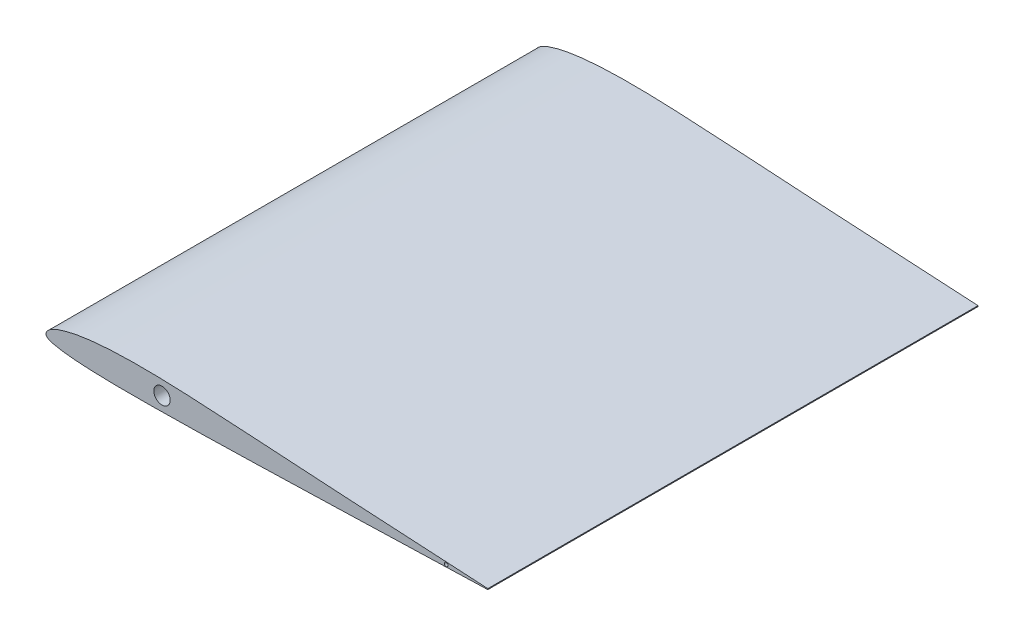
SolidWorks part; units mm, degrees
material "Polyurethane Foam Flexible"
ref_plane "Front Plane" through (0, 0, 0) normal (0, 0, 1) x (1, 0, 0)
ref_plane "Top Plane" through (0, 0, 0) normal (0, 1, 0) x (1, 0, 0)
ref_plane "Right Plane" through (0, 0, 0) normal (1, 0, 0) x (0, 0, -1)
curve "ht32-8-imported"
  spline degree 3 poles (203.2026, 0.2115, 0) (202.75, 0.2358, 0) (201.4822, 0.3036, 0) (199.2299, 0.4276, 0) (196.3046, 0.5865, 0) (192.9787, 0.7694, 0) (189.375, 0.9706, 0) (185.6129, 1.1785, 0) (181.7737, 1.3957, 0) (177.8996, 1.6147, 0) (174.01, 1.8354, 0) (170.1132, 2.0552, 0) (166.2133, 2.2775, 0) (162.3117, 2.4986, 0) (158.4107, 2.722, 0) (154.5106, 2.9441, 0) (150.6142, 3.1678, 0) (146.7204, 3.3936, 0) (142.8309, 3.617, 0) (138.944, 3.8454, 0) (135.0595, 4.0721, 0) (131.1775, 4.3012, 0) (127.2967, 4.5315, 0) (123.4189, 4.7649, 0) (119.5421, 5.0008, 0) (115.6675, 5.2398, 0) (111.7949, 5.4816, 0) (107.9236, 5.7247, 0) (104.0572, 5.9681, 0) (100.1894, 6.212, 0) (96.3188, 6.4543, 0) (92.4477, 6.6946, 0) (88.584, 6.9322, 0) (84.7415, 7.1637, 0) (80.9229, 7.3889, 0) (77.3978, 7.5906, 0) (74.5229, 7.7493, 0) (71.9946, 7.8843, 0) (69.1241, 8.0324, 0) (65.5083, 8.2076, 0) (61.4852, 8.3831, 0) (57.5218, 8.5328, 0) (53.6734, 8.652, 0) (49.9058, 8.739, 0) (46.181, 8.7912, 0) (42.491, 8.8047, 0) (38.8468, 8.7742, 0) (35.2596, 8.6962, 0) (31.7561, 8.5671, 0) (28.3661, 8.3856, 0) (25.1292, 8.152, 0) (22.0798, 7.8688, 0) (19.2587, 7.5428, 0) (16.7019, 7.1837, 0) (14.4336, 6.8058, 0) (12.4541, 6.4216, 0) (10.7471, 6.0418, 0) (9.283, 5.6741, 0) (8.0264, 5.3216, 0) (6.9394, 4.9844, 0) (5.9876, 4.6599, 0) (5.1429, 4.3427, 0) (4.3754, 4.0301, 0) (3.6577, 3.7081, 0) (2.9646, 3.3607, 0) (2.2868, 2.9708, 0) (1.6384, 2.5305, 0) (1.05, 2.0355, 0) (0.5511, 1.4823, 0) (0.1821, 0.8795, 0) (0.0202, 0.3651, 0) (-0.0065, -0.0193, 0) (0.0194, -0.3136, 0) (0.1268, -0.6144, 0) (0.297, -0.8546, 0) (0.4742, -1.036, 0) (0.6922, -1.2054, 0) (0.9846, -1.3848, 0) (1.3525, -1.5668, 0) (1.7794, -1.7448, 0) (2.2605, -1.9172, 0) (2.8067, -2.0876, 0) (3.4413, -2.2602, 0) (4.1881, -2.438, 0) (5.0669, -2.6215, 0) (6.0922, -2.8069, 0) (7.2766, -2.9931, 0) (8.6343, -3.178, 0) (10.1869, -3.3594, 0) (11.9608, -3.5369, 0) (13.9882, -3.7077, 0) (16.2949, -3.8689, 0) (18.8937, -4.0155, 0) (21.7662, -4.1437, 0) (24.8729, -4.2492, 0) (28.1584, -4.3297, 0) (31.5775, -4.3867, 0) (35.0914, -4.4207, 0) (38.6791, -4.4351, 0) (42.3216, -4.4311, 0) (46.0126, -4.4125, 0) (49.7579, -4.3795, 0) (53.5805, -4.3372, 0) (57.5149, -4.2842, 0) (61.5959, -4.2202, 0) (65.8841, -4.1445, 0) (69.584, -4.0721, 0) (72.8088, -4.005, 0) (75.5799, -3.9448, 0) (78.7708, -3.8727, 0) (82.2137, -3.7909, 0) (85.8123, -3.7021, 0) (89.4548, -3.6091, 0) (93.1502, -3.5116, 0) (96.8889, -3.4111, 0) (100.657, -3.3069, 0) (104.4397, -3.2018, 0) (108.2248, -3.0945, 0) (112.0082, -2.9863, 0) (115.791, -2.8766, 0) (119.5782, -2.7658, 0) (123.3765, -2.6523, 0) (127.1945, -2.5376, 0) (131.0416, -2.42, 0) (134.9198, -2.302, 0) (138.8194, -2.1823, 0) (142.7263, -2.0602, 0) (146.6334, -1.9373, 0) (150.5405, -1.8169, 0) (154.4476, -1.6935, 0) (158.3547, -1.5735, 0) (162.2615, -1.4515, 0) (166.1675, -1.3317, 0) (170.0718, -1.2089, 0) (173.9729, -1.0897, 0) (177.8669, -0.9678, 0) (181.7453, -0.8488, 0) (185.5889, -0.7312, 0) (189.3549, -0.6169, 0) (192.9626, -0.5096, 0) (196.292, -0.413, 0) (199.2203, -0.3248, 0) (201.4752, -0.2617, 0) (202.7443, -0.2247, 0) (203.1974, -0.2115, 0) knots 0 0 0 0 0.003316 0.009286 0.0165 0.024744 0.033651 0.0429 0.052304 0.061778 0.071282 0.080801 0.090326 0.099855 0.109385 0.118907 0.128429 0.137932 0.147436 0.156926 0.166412 0.175898 0.185369 0.194848 0.204314 0.213779 0.223243 0.232695 0.242152 0.25158 0.261042 0.270519 0.279949 0.289356 0.298677 0.307928 0.315183 0.319737 0.326448 0.336207 0.346216 0.355902 0.365219 0.374379 0.383467 0.392467 0.401369 0.410123 0.41871 0.427012 0.434953 0.442447 0.449411 0.455723 0.46133 0.466229 0.470471 0.47412 0.47727 0.480016 0.482444 0.484624 0.486615 0.488504 0.490376 0.492284 0.49422 0.496102 0.497896 0.499646 0.501237 0.501776 0.502457 0.503386 0.504071 0.504595 0.505236 0.506086 0.5071 0.508235 0.509467 0.510837 0.512419 0.514277 0.516452 0.518985 0.521897 0.525221 0.529007 0.53333 0.538261 0.543889 0.550243 0.557299 0.56492 0.57298 0.581338 0.589931 0.598683 0.607581 0.616575 0.625681 0.634977 0.644537 0.654462 0.664831 0.675908 0.681531 0.688425 0.696181 0.704877 0.713615 0.722511 0.731528 0.740655 0.749867 0.759101 0.768335 0.777565 0.786786 0.796016 0.805278 0.814581 0.823955 0.833431 0.842961 0.852492 0.862023 0.871554 0.881085 0.890615 0.900146 0.909675 0.9192 0.928718 0.938223 0.947696 0.9571 0.96635 0.975256 0.9835 0.990713 0.996685 1 1 1 1
sketch "Sketch3" plane through (0, 0, 0) normal (0, 0, 1) x (1, 0, 0)
  line L3 (203.2026, 0.2115) -> (203.1974, -0.2115)
  spline S0 degree 3 poles (356.7908, -2985.9067) (413.0686, 1.836) (306.2858, -5.4633) (199.2299, 0.4276) (196.3046, 0.5865) (192.9787, 0.7694) (189.375, 0.9706) (185.6129, 1.1785) (181.7737, 1.3957) (177.8996, 1.6147) (174.01, 1.8354) (170.1132, 2.0552) (166.2133, 2.2775) (162.3117, 2.4986) (158.4107, 2.722) (154.5106, 2.9441) (150.6142, 3.1678) (146.7204, 3.3936) (142.8309, 3.617) (138.944, 3.8454) (135.0595, 4.0721) (131.1775, 4.3012) (127.2967, 4.5315) (123.4189, 4.7649) (119.5421, 5.0008) (115.6675, 5.2398) (111.7949, 5.4816) (107.9236, 5.7247) (104.0572, 5.9681) (100.1894, 6.212) (96.3188, 6.4543) (92.4477, 6.6946) (88.584, 6.9322) (84.7415, 7.1637) (80.9229, 7.3889) (77.3978, 7.5906) (74.5229, 7.7493) (71.9946, 7.8843) (69.1241, 8.0324) (65.5083, 8.2076) (61.4852, 8.3831) (57.5218, 8.5328) (53.6734, 8.652) (49.9058, 8.739) (46.181, 8.7912) (42.491, 8.8047) (38.8468, 8.7742) (35.2596, 8.6962) (31.7561, 8.5671) (28.3661, 8.3856) (25.1292, 8.152) (22.0798, 7.8688) (19.2587, 7.5428) (16.7019, 7.1837) (14.4336, 6.8058) (12.4541, 6.4216) (10.7471, 6.0418) (9.283, 5.6741) (8.0264, 5.3216) (6.9394, 4.9844) (5.9876, 4.6599) (5.1429, 4.3427) (4.3754, 4.0301) (3.6577, 3.7081) (2.9646, 3.3607) (2.2868, 2.9708) (1.6384, 2.5305) (1.05, 2.0355) (0.5511, 1.4823) (0.1821, 0.8795) (0.0202, 0.3651) (-0.0065, -0.0193) (0.0194, -0.3136) (0.1268, -0.6144) (0.297, -0.8546) (0.4742, -1.036) (0.6922, -1.2054) (0.9846, -1.3848) (1.3525, -1.5668) (1.7794, -1.7448) (2.2605, -1.9172) (2.8067, -2.0876) (3.4413, -2.2602) (4.1881, -2.438) (5.0669, -2.6215) (6.0922, -2.8069) (7.2766, -2.9931) (8.6343, -3.178) (10.1869, -3.3594) (11.9608, -3.5369) (13.9882, -3.7077) (16.2949, -3.8689) (18.8937, -4.0155) (21.7662, -4.1437) (24.8729, -4.2492) (28.1584, -4.3297) (31.5775, -4.3867) (35.0914, -4.4207) (38.6791, -4.4351) (42.3216, -4.4311) (46.0126, -4.4125) (49.7579, -4.3795) (53.5805, -4.3372) (57.5149, -4.2842) (61.5959, -4.2202) (65.8841, -4.1445) (69.584, -4.0721) (72.8088, -4.005) (75.5799, -3.9448) (78.7708, -3.8727) (82.2137, -3.7909) (85.8123, -3.7021) (89.4548, -3.6091) (93.1502, -3.5116) (96.8889, -3.4111) (100.657, -3.3069) (104.4397, -3.2018) (108.2248, -3.0945) (112.0082, -2.9863) (115.791, -2.8766) (119.5782, -2.7658) (123.3765, -2.6523) (127.1945, -2.5376) (131.0416, -2.42) (134.9198, -2.302) (138.8194, -2.1823) (142.7263, -2.0602) (146.6334, -1.9373) (150.5405, -1.8169) (154.4476, -1.6935) (158.3547, -1.5735) (162.2615, -1.4515) (166.1675, -1.3317) (170.0718, -1.2089) (173.9729, -1.0897) (177.8669, -0.9678) (181.7453, -0.8488) (185.5889, -0.7312) (189.3549, -0.6169) (192.9626, -0.5096) (196.292, -0.413) (199.2203, -0.3248) (315.412, 2.9269) (430.2694, 18.2159) (630.7155, -2957.7378) knots -0.767748 -0.767748 -0.767748 -0.767748 0.003316 0.009286 0.0165 0.024744 0.033651 0.0429 0.052304 0.061778 0.071282 0.080801 0.090326 0.099855 0.109385 0.118907 0.128429 0.137932 0.147436 0.156926 0.166412 0.175898 0.185369 0.194848 0.204314 0.213779 0.223243 0.232695 0.242152 0.25158 0.261042 0.270519 0.279949 0.289356 0.298677 0.307928 0.315183 0.319737 0.326448 0.336207 0.346216 0.355902 0.365219 0.374379 0.383467 0.392467 0.401369 0.410123 0.41871 0.427012 0.434953 0.442447 0.449411 0.455723 0.46133 0.466229 0.470471 0.47412 0.47727 0.480016 0.482444 0.484624 0.486615 0.488504 0.490376 0.492284 0.49422 0.496102 0.497896 0.499646 0.501237 0.501776 0.502457 0.503386 0.504071 0.504595 0.505236 0.506086 0.5071 0.508235 0.509467 0.510837 0.512419 0.514277 0.516452 0.518985 0.521897 0.525221 0.529007 0.53333 0.538261 0.543889 0.550243 0.557299 0.56492 0.57298 0.581338 0.589931 0.598683 0.607581 0.616575 0.625681 0.634977 0.644537 0.654462 0.664831 0.675908 0.681531 0.688425 0.696181 0.704877 0.713615 0.722511 0.731528 0.740655 0.749867 0.759101 0.768335 0.777565 0.786786 0.796016 0.805278 0.814581 0.823955 0.833431 0.842961 0.852492 0.862023 0.871554 0.881085 0.890615 0.900146 0.909675 0.9192 0.928718 0.938223 0.947696 0.9571 0.96635 0.975256 0.9835 0.990713 0.996685 1.83372 1.83372 1.83372 1.83372 only from (203.2026, 0.2115) to (203.1974, -0.2115) construction
  spline S1 degree 3 poles (203.2026, 0.2115) (202.75, 0.2358) (201.4822, 0.3036) (199.2299, 0.4276) (196.3046, 0.5865) (192.9787, 0.7694) (189.375, 0.9706) (185.6129, 1.1785) (181.7737, 1.3957) (177.8996, 1.6147) (174.01, 1.8354) (170.1132, 2.0552) (166.2133, 2.2775) (162.3117, 2.4986) (158.4107, 2.722) (154.5106, 2.9441) (150.6142, 3.1678) (146.7204, 3.3936) (142.8309, 3.617) (138.944, 3.8454) (135.0595, 4.0721) (131.1775, 4.3012) (127.2967, 4.5315) (123.4189, 4.7649) (119.5421, 5.0008) (115.6675, 5.2398) (111.7949, 5.4816) (107.9236, 5.7247) (104.0572, 5.9681) (100.1894, 6.212) (96.3188, 6.4543) (92.4477, 6.6946) (88.584, 6.9322) (84.7415, 7.1637) (80.9229, 7.3889) (77.3978, 7.5906) (74.5229, 7.7493) (71.9946, 7.8843) (69.1241, 8.0324) (65.5083, 8.2076) (61.4852, 8.3831) (57.5218, 8.5328) (53.6734, 8.652) (49.9058, 8.739) (46.181, 8.7912) (42.491, 8.8047) (38.8468, 8.7742) (35.2596, 8.6962) (31.7561, 8.5671) (28.3661, 8.3856) (25.1292, 8.152) (22.0798, 7.8688) (19.2587, 7.5428) (16.7019, 7.1837) (14.4336, 6.8058) (12.4541, 6.4216) (10.7471, 6.0418) (9.283, 5.6741) (8.0264, 5.3216) (6.9394, 4.9844) (5.9876, 4.6599) (5.1429, 4.3427) (4.3754, 4.0301) (3.6577, 3.7081) (2.9646, 3.3607) (2.2868, 2.9708) (1.6384, 2.5305) (1.05, 2.0355) (0.5511, 1.4823) (0.1821, 0.8795) (0.0202, 0.3651) (-0.0065, -0.0193) (0.0194, -0.3136) (0.1268, -0.6144) (0.297, -0.8546) (0.4742, -1.036) (0.6922, -1.2054) (0.9846, -1.3848) (1.3525, -1.5668) (1.7794, -1.7448) (2.2605, -1.9172) (2.8067, -2.0876) (3.4413, -2.2602) (4.1881, -2.438) (5.0669, -2.6215) (6.0922, -2.8069) (7.2766, -2.9931) (8.6343, -3.178) (10.1869, -3.3594) (11.9608, -3.5369) (13.9882, -3.7077) (16.2949, -3.8689) (18.8937, -4.0155) (21.7662, -4.1437) (24.8729, -4.2492) (28.1584, -4.3297) (31.5775, -4.3867) (35.0914, -4.4207) (38.6791, -4.4351) (42.3216, -4.4311) (46.0126, -4.4125) (49.7579, -4.3795) (53.5805, -4.3372) (57.5149, -4.2842) (61.5959, -4.2202) (65.8841, -4.1445) (69.584, -4.0721) (72.8088, -4.005) (75.5799, -3.9448) (78.7708, -3.8727) (82.2137, -3.7909) (85.8123, -3.7021) (89.4548, -3.6091) (93.1502, -3.5116) (96.8889, -3.4111) (100.657, -3.3069) (104.4397, -3.2018) (108.2248, -3.0945) (112.0082, -2.9863) (115.791, -2.8766) (119.5782, -2.7658) (123.3765, -2.6523) (127.1945, -2.5376) (131.0416, -2.42) (134.9198, -2.302) (138.8194, -2.1823) (142.7263, -2.0602) (146.6334, -1.9373) (150.5405, -1.8169) (154.4476, -1.6935) (158.3547, -1.5735) (162.2615, -1.4515) (166.1675, -1.3317) (170.0718, -1.2089) (173.9729, -1.0897) (177.8669, -0.9678) (181.7453, -0.8488) (185.5889, -0.7312) (189.3549, -0.6169) (192.9626, -0.5096) (196.292, -0.413) (199.2203, -0.3248) (201.4752, -0.2617) (202.7443, -0.2247) (203.1974, -0.2115) knots 0 0 0 0 0.003316 0.009286 0.0165 0.024744 0.033651 0.0429 0.052304 0.061778 0.071282 0.080801 0.090326 0.099855 0.109385 0.118907 0.128429 0.137932 0.147436 0.156926 0.166412 0.175898 0.185369 0.194848 0.204314 0.213779 0.223243 0.232695 0.242152 0.25158 0.261042 0.270519 0.279949 0.289356 0.298677 0.307928 0.315183 0.319737 0.326448 0.336207 0.346216 0.355902 0.365219 0.374379 0.383467 0.392467 0.401369 0.410123 0.41871 0.427012 0.434953 0.442447 0.449411 0.455723 0.46133 0.466229 0.470471 0.47412 0.47727 0.480016 0.482444 0.484624 0.486615 0.488504 0.490376 0.492284 0.49422 0.496102 0.497896 0.499646 0.501237 0.501776 0.502457 0.503386 0.504071 0.504595 0.505236 0.506086 0.5071 0.508235 0.509467 0.510837 0.512419 0.514277 0.516452 0.518985 0.521897 0.525221 0.529007 0.53333 0.538261 0.543889 0.550243 0.557299 0.56492 0.57298 0.581338 0.589931 0.598683 0.607581 0.616575 0.625681 0.634977 0.644537 0.654462 0.664831 0.675908 0.681531 0.688425 0.696181 0.704877 0.713615 0.722511 0.731528 0.740655 0.749867 0.759101 0.768335 0.777565 0.786786 0.796016 0.805278 0.814581 0.823955 0.833431 0.842961 0.852492 0.862023 0.871554 0.881085 0.890615 0.900146 0.909675 0.9192 0.928718 0.938223 0.947696 0.9571 0.96635 0.975256 0.9835 0.990713 0.996685 1 1 1 1
extrude "Airfoil" add sketch "Sketch3" along normal blind 225.425
sketch "Sketch8" plane through (0, 0, 0) normal (0, 0, -1) x (-1, 0, 0)
  line L0 (0, 16.6795) -> (0, -1.637) construction
  line L2 (-53.34, 2.1587) -> (-53.34, 8.6559) construction
  line L3 (-53.34, 2.1587) -> (-53.34, -4.3386) construction
  circle A0 centre (-53.34, 2.1587) radius 3.7592
  spline S2 degree 3 poles (-203.2026, 0.2115) (-202.75, 0.2358) (-201.4822, 0.3036) (-199.2299, 0.4276) (-196.3046, 0.5865) (-192.9787, 0.7694) (-189.375, 0.9706) (-185.6129, 1.1785) (-181.7737, 1.3957) (-177.8996, 1.6147) (-174.01, 1.8354) (-170.1132, 2.0552) (-166.2133, 2.2775) (-162.3117, 2.4986) (-158.4107, 2.722) (-154.5106, 2.9441) (-150.6142, 3.1678) (-146.7204, 3.3936) (-142.8309, 3.617) (-138.944, 3.8454) (-135.0595, 4.0721) (-131.1775, 4.3012) (-127.2967, 4.5315) (-123.4189, 4.7649) (-119.5421, 5.0008) (-115.6675, 5.2398) (-111.7949, 5.4816) (-107.9236, 5.7247) (-104.0572, 5.9681) (-100.1894, 6.212) (-96.3188, 6.4543) (-92.4477, 6.6946) (-88.584, 6.9322) (-84.7415, 7.1637) (-80.9229, 7.3889) (-77.3978, 7.5906) (-74.5229, 7.7493) (-71.9946, 7.8843) (-69.1241, 8.0324) (-65.5083, 8.2076) (-61.4852, 8.3831) (-57.5218, 8.5328) (-53.6734, 8.652) (-49.9058, 8.739) (-46.181, 8.7912) (-42.491, 8.8047) (-38.8468, 8.7742) (-35.2596, 8.6962) (-31.7561, 8.5671) (-28.3661, 8.3856) (-25.1292, 8.152) (-22.0798, 7.8688) (-19.2587, 7.5428) (-16.7019, 7.1837) (-14.4336, 6.8058) (-12.4541, 6.4216) (-10.7471, 6.0418) (-9.283, 5.6741) (-8.0264, 5.3216) (-6.9394, 4.9844) (-5.9876, 4.6599) (-5.1429, 4.3427) (-4.3754, 4.0301) (-3.6577, 3.7081) (-2.9646, 3.3607) (-2.2868, 2.9708) (-1.6384, 2.5305) (-1.05, 2.0355) (-0.5511, 1.4823) (-0.1821, 0.8795) (-0.0202, 0.3651) (0.0065, -0.0193) (-0.0194, -0.3136) (-0.1268, -0.6144) (-0.297, -0.8546) (-0.4742, -1.036) (-0.6922, -1.2054) (-0.9846, -1.3848) (-1.3525, -1.5668) (-1.7794, -1.7448) (-2.2605, -1.9172) (-2.8067, -2.0876) (-3.4413, -2.2602) (-4.1881, -2.438) (-5.0669, -2.6215) (-6.0922, -2.8069) (-7.2766, -2.9931) (-8.6343, -3.178) (-10.1869, -3.3594) (-11.9608, -3.5369) (-13.9882, -3.7077) (-16.2949, -3.8689) (-18.8937, -4.0155) (-21.7662, -4.1437) (-24.8729, -4.2492) (-28.1584, -4.3297) (-31.5775, -4.3867) (-35.0914, -4.4207) (-38.6791, -4.4351) (-42.3216, -4.4311) (-46.0126, -4.4125) (-49.7579, -4.3795) (-53.5805, -4.3372) (-57.5149, -4.2842) (-61.5959, -4.2202) (-65.8841, -4.1445) (-69.584, -4.0721) (-72.8088, -4.005) (-75.5799, -3.9448) (-78.7708, -3.8727) (-82.2137, -3.7909) (-85.8123, -3.7021) (-89.4548, -3.6091) (-93.1502, -3.5116) (-96.8889, -3.4111) (-100.657, -3.3069) (-104.4397, -3.2018) (-108.2248, -3.0945) (-112.0082, -2.9863) (-115.791, -2.8766) (-119.5782, -2.7658) (-123.3765, -2.6523) (-127.1945, -2.5376) (-131.0416, -2.42) (-134.9198, -2.302) (-138.8194, -2.1823) (-142.7263, -2.0602) (-146.6334, -1.9373) (-150.5405, -1.8169) (-154.4476, -1.6935) (-158.3547, -1.5735) (-162.2615, -1.4515) (-166.1675, -1.3317) (-170.0718, -1.2089) (-173.9729, -1.0897) (-177.8669, -0.9678) (-181.7453, -0.8488) (-185.5889, -0.7312) (-189.3549, -0.6169) (-192.9626, -0.5096) (-196.292, -0.413) (-199.2203, -0.3248) (-201.4752, -0.2617) (-202.7443, -0.2247) (-203.1974, -0.2115) knots 0 0 0 0 0.003316 0.009286 0.0165 0.024744 0.033651 0.0429 0.052304 0.061778 0.071282 0.080801 0.090326 0.099855 0.109385 0.118907 0.128429 0.137932 0.147436 0.156926 0.166412 0.175898 0.185369 0.194848 0.204314 0.213779 0.223243 0.232695 0.242152 0.25158 0.261042 0.270519 0.279949 0.289356 0.298677 0.307928 0.315183 0.319737 0.326448 0.336207 0.346216 0.355902 0.365219 0.374379 0.383467 0.392467 0.401369 0.410123 0.41871 0.427012 0.434953 0.442447 0.449411 0.455723 0.46133 0.466229 0.470471 0.47412 0.47727 0.480016 0.482444 0.484624 0.486615 0.488504 0.490376 0.492284 0.49422 0.496102 0.497896 0.499646 0.501237 0.501776 0.502457 0.503386 0.504071 0.504595 0.505236 0.506086 0.5071 0.508235 0.509467 0.510837 0.512419 0.514277 0.516452 0.518985 0.521897 0.525221 0.529007 0.53333 0.538261 0.543889 0.550243 0.557299 0.56492 0.57298 0.581338 0.589931 0.598683 0.607581 0.616575 0.625681 0.634977 0.644537 0.654462 0.664831 0.675908 0.681531 0.688425 0.696181 0.704877 0.713615 0.722511 0.731528 0.740655 0.749867 0.759101 0.768335 0.777565 0.786786 0.796016 0.805278 0.814581 0.823955 0.833431 0.842961 0.852492 0.862023 0.871554 0.881085 0.890615 0.900146 0.909675 0.9192 0.928718 0.938223 0.947696 0.9571 0.96635 0.975256 0.9835 0.990713 0.996685 1 1 1 1 construction
  dimension "D1" = 7.5184
  dimension "D2" = 53.34
extrude "Camera Channel" cut sketch "Sketch8" against normal up to next
sketch "Sketch9" plane through (0, 0, 0) normal (0, 0, -1) x (-1, 0, 0)
  line L0 (-184.051, 1.108) -> (-184.051, 1.2671) construction
  line L1 (-184.051, -0.6192) -> (-184.051, -0.7783) construction
  circle A0 centre (-184.051, 0.2444) radius 0.8636
  spline S0 degree 3 poles (-370.7177, -1986.1352) (-386.1593, 0.2045) (-292.9152, -4.7275) (-199.2299, 0.4276) (-196.3046, 0.5865) (-192.9787, 0.7694) (-189.375, 0.9706) (-185.6129, 1.1785) (-181.7737, 1.3957) (-177.8996, 1.6147) (-174.01, 1.8354) (-170.1132, 2.0552) (-166.2133, 2.2775) (-162.3117, 2.4986) (-158.4107, 2.722) (-154.5106, 2.9441) (-150.6142, 3.1678) (-146.7204, 3.3936) (-142.8309, 3.617) (-138.944, 3.8454) (-135.0595, 4.0721) (-131.1775, 4.3012) (-127.2967, 4.5315) (-123.4189, 4.7649) (-119.5421, 5.0008) (-115.6675, 5.2398) (-111.7949, 5.4816) (-107.9236, 5.7247) (-104.0572, 5.9681) (-100.1894, 6.212) (-96.3188, 6.4543) (-92.4477, 6.6946) (-88.584, 6.9322) (-84.7415, 7.1637) (-80.9229, 7.3889) (-77.3978, 7.5906) (-74.5229, 7.7493) (-71.9946, 7.8843) (-69.1241, 8.0324) (-65.5083, 8.2076) (-61.4852, 8.3831) (-57.5218, 8.5328) (-53.6734, 8.652) (-49.9058, 8.739) (-46.181, 8.7912) (-42.491, 8.8047) (-38.8468, 8.7742) (-35.2596, 8.6962) (-31.7561, 8.5671) (-28.3661, 8.3856) (-25.1292, 8.152) (-22.0798, 7.8688) (-19.2587, 7.5428) (-16.7019, 7.1837) (-14.4336, 6.8058) (-12.4541, 6.4216) (-10.7471, 6.0418) (-9.283, 5.6741) (-8.0264, 5.3216) (-6.9394, 4.9844) (-5.9876, 4.6599) (-5.1429, 4.3427) (-4.3754, 4.0301) (-3.6577, 3.7081) (-2.9646, 3.3607) (-2.2868, 2.9708) (-1.6384, 2.5305) (-1.05, 2.0355) (-0.5511, 1.4823) (-0.1821, 0.8795) (-0.0202, 0.3651) (0.0065, -0.0193) (-0.0194, -0.3136) (-0.1268, -0.6144) (-0.297, -0.8546) (-0.4742, -1.036) (-0.6922, -1.2054) (-0.9846, -1.3848) (-1.3525, -1.5668) (-1.7794, -1.7448) (-2.2605, -1.9172) (-2.8067, -2.0876) (-3.4413, -2.2602) (-4.1881, -2.438) (-5.0669, -2.6215) (-6.0922, -2.8069) (-7.2766, -2.9931) (-8.6343, -3.178) (-10.1869, -3.3594) (-11.9608, -3.5369) (-13.9882, -3.7077) (-16.2949, -3.8689) (-18.8937, -4.0155) (-21.7662, -4.1437) (-24.8729, -4.2492) (-28.1584, -4.3297) (-31.5775, -4.3867) (-35.0914, -4.4207) (-38.6791, -4.4351) (-42.3216, -4.4311) (-46.0126, -4.4125) (-49.7579, -4.3795) (-53.5805, -4.3372) (-57.5149, -4.2842) (-61.5959, -4.2202) (-65.8841, -4.1445) (-69.584, -4.0721) (-72.8088, -4.005) (-75.5799, -3.9448) (-78.7708, -3.8727) (-82.2137, -3.7909) (-85.8123, -3.7021) (-89.4548, -3.6091) (-93.1502, -3.5116) (-96.8889, -3.4111) (-100.657, -3.3069) (-104.4397, -3.2018) (-108.2248, -3.0945) (-112.0082, -2.9863) (-115.791, -2.8766) (-119.5782, -2.7658) (-123.3765, -2.6523) (-127.1945, -2.5376) (-131.0416, -2.42) (-134.9198, -2.302) (-138.8194, -2.1823) (-142.7263, -2.0602) (-146.6334, -1.9373) (-150.5405, -1.8169) (-154.4476, -1.6935) (-158.3547, -1.5735) (-162.2615, -1.4515) (-166.1675, -1.3317) (-170.0718, -1.2089) (-173.9729, -1.0897) (-177.8669, -0.9678) (-181.7453, -0.8488) (-185.5889, -0.7312) (-189.3549, -0.6169) (-192.9626, -0.5096) (-196.292, -0.413) (-199.2203, -0.3248) (-300.851, 2.5194) (-401.2299, 14.5438) (-558.1905, -1960.49) knots -0.669801 -0.669801 -0.669801 -0.669801 0.003316 0.009286 0.0165 0.024744 0.033651 0.0429 0.052304 0.061778 0.071282 0.080801 0.090326 0.099855 0.109385 0.118907 0.128429 0.137932 0.147436 0.156926 0.166412 0.175898 0.185369 0.194848 0.204314 0.213779 0.223243 0.232695 0.242152 0.25158 0.261042 0.270519 0.279949 0.289356 0.298677 0.307928 0.315183 0.319737 0.326448 0.336207 0.346216 0.355902 0.365219 0.374379 0.383467 0.392467 0.401369 0.410123 0.41871 0.427012 0.434953 0.442447 0.449411 0.455723 0.46133 0.466229 0.470471 0.47412 0.47727 0.480016 0.482444 0.484624 0.486615 0.488504 0.490376 0.492284 0.49422 0.496102 0.497896 0.499646 0.501237 0.501776 0.502457 0.503386 0.504071 0.504595 0.505236 0.506086 0.5071 0.508235 0.509467 0.510837 0.512419 0.514277 0.516452 0.518985 0.521897 0.525221 0.529007 0.53333 0.538261 0.543889 0.550243 0.557299 0.56492 0.57298 0.581338 0.589931 0.598683 0.607581 0.616575 0.625681 0.634977 0.644537 0.654462 0.664831 0.675908 0.681531 0.688425 0.696181 0.704877 0.713615 0.722511 0.731528 0.740655 0.749867 0.759101 0.768335 0.777565 0.786786 0.796016 0.805278 0.814581 0.823955 0.833431 0.842961 0.852492 0.862023 0.871554 0.881085 0.890615 0.900146 0.909675 0.9192 0.928718 0.938223 0.947696 0.9571 0.96635 0.975256 0.9835 0.990713 0.996685 1.727171 1.727171 1.727171 1.727171 only from (-203.2026, 0.2115) to (-203.1974, -0.2115) construction
  spline S1 degree 3 poles (-203.2026, 0.2115) (-202.75, 0.2358) (-201.4822, 0.3036) (-199.2299, 0.4276) (-196.3046, 0.5865) (-192.9787, 0.7694) (-189.375, 0.9706) (-185.6129, 1.1785) (-181.7737, 1.3957) (-177.8996, 1.6147) (-174.01, 1.8354) (-170.1132, 2.0552) (-166.2133, 2.2775) (-162.3117, 2.4986) (-158.4107, 2.722) (-154.5106, 2.9441) (-150.6142, 3.1678) (-146.7204, 3.3936) (-142.8309, 3.617) (-138.944, 3.8454) (-135.0595, 4.0721) (-131.1775, 4.3012) (-127.2967, 4.5315) (-123.4189, 4.7649) (-119.5421, 5.0008) (-115.6675, 5.2398) (-111.7949, 5.4816) (-107.9236, 5.7247) (-104.0572, 5.9681) (-100.1894, 6.212) (-96.3188, 6.4543) (-92.4477, 6.6946) (-88.584, 6.9322) (-84.7415, 7.1637) (-80.9229, 7.3889) (-77.3978, 7.5906) (-74.5229, 7.7493) (-71.9946, 7.8843) (-69.1241, 8.0324) (-65.5083, 8.2076) (-61.4852, 8.3831) (-57.5218, 8.5328) (-53.6734, 8.652) (-49.9058, 8.739) (-46.181, 8.7912) (-42.491, 8.8047) (-38.8468, 8.7742) (-35.2596, 8.6962) (-31.7561, 8.5671) (-28.3661, 8.3856) (-25.1292, 8.152) (-22.0798, 7.8688) (-19.2587, 7.5428) (-16.7019, 7.1837) (-14.4336, 6.8058) (-12.4541, 6.4216) (-10.7471, 6.0418) (-9.283, 5.6741) (-8.0264, 5.3216) (-6.9394, 4.9844) (-5.9876, 4.6599) (-5.1429, 4.3427) (-4.3754, 4.0301) (-3.6577, 3.7081) (-2.9646, 3.3607) (-2.2868, 2.9708) (-1.6384, 2.5305) (-1.05, 2.0355) (-0.5511, 1.4823) (-0.1821, 0.8795) (-0.0202, 0.3651) (0.0065, -0.0193) (-0.0194, -0.3136) (-0.1268, -0.6144) (-0.297, -0.8546) (-0.4742, -1.036) (-0.6922, -1.2054) (-0.9846, -1.3848) (-1.3525, -1.5668) (-1.7794, -1.7448) (-2.2605, -1.9172) (-2.8067, -2.0876) (-3.4413, -2.2602) (-4.1881, -2.438) (-5.0669, -2.6215) (-6.0922, -2.8069) (-7.2766, -2.9931) (-8.6343, -3.178) (-10.1869, -3.3594) (-11.9608, -3.5369) (-13.9882, -3.7077) (-16.2949, -3.8689) (-18.8937, -4.0155) (-21.7662, -4.1437) (-24.8729, -4.2492) (-28.1584, -4.3297) (-31.5775, -4.3867) (-35.0914, -4.4207) (-38.6791, -4.4351) (-42.3216, -4.4311) (-46.0126, -4.4125) (-49.7579, -4.3795) (-53.5805, -4.3372) (-57.5149, -4.2842) (-61.5959, -4.2202) (-65.8841, -4.1445) (-69.584, -4.0721) (-72.8088, -4.005) (-75.5799, -3.9448) (-78.7708, -3.8727) (-82.2137, -3.7909) (-85.8123, -3.7021) (-89.4548, -3.6091) (-93.1502, -3.5116) (-96.8889, -3.4111) (-100.657, -3.3069) (-104.4397, -3.2018) (-108.2248, -3.0945) (-112.0082, -2.9863) (-115.791, -2.8766) (-119.5782, -2.7658) (-123.3765, -2.6523) (-127.1945, -2.5376) (-131.0416, -2.42) (-134.9198, -2.302) (-138.8194, -2.1823) (-142.7263, -2.0602) (-146.6334, -1.9373) (-150.5405, -1.8169) (-154.4476, -1.6935) (-158.3547, -1.5735) (-162.2615, -1.4515) (-166.1675, -1.3317) (-170.0718, -1.2089) (-173.9729, -1.0897) (-177.8669, -0.9678) (-181.7453, -0.8488) (-185.5889, -0.7312) (-189.3549, -0.6169) (-192.9626, -0.5096) (-196.292, -0.413) (-199.2203, -0.3248) (-201.4752, -0.2617) (-202.7443, -0.2247) (-203.1974, -0.2115) knots 0 0 0 0 0.003316 0.009286 0.0165 0.024744 0.033651 0.0429 0.052304 0.061778 0.071282 0.080801 0.090326 0.099855 0.109385 0.118907 0.128429 0.137932 0.147436 0.156926 0.166412 0.175898 0.185369 0.194848 0.204314 0.213779 0.223243 0.232695 0.242152 0.25158 0.261042 0.270519 0.279949 0.289356 0.298677 0.307928 0.315183 0.319737 0.326448 0.336207 0.346216 0.355902 0.365219 0.374379 0.383467 0.392467 0.401369 0.410123 0.41871 0.427012 0.434953 0.442447 0.449411 0.455723 0.46133 0.466229 0.470471 0.47412 0.47727 0.480016 0.482444 0.484624 0.486615 0.488504 0.490376 0.492284 0.49422 0.496102 0.497896 0.499646 0.501237 0.501776 0.502457 0.503386 0.504071 0.504595 0.505236 0.506086 0.5071 0.508235 0.509467 0.510837 0.512419 0.514277 0.516452 0.518985 0.521897 0.525221 0.529007 0.53333 0.538261 0.543889 0.550243 0.557299 0.56492 0.57298 0.581338 0.589931 0.598683 0.607581 0.616575 0.625681 0.634977 0.644537 0.654462 0.664831 0.675908 0.681531 0.688425 0.696181 0.704877 0.713615 0.722511 0.731528 0.740655 0.749867 0.759101 0.768335 0.777565 0.786786 0.796016 0.805278 0.814581 0.823955 0.833431 0.842961 0.852492 0.862023 0.871554 0.881085 0.890615 0.900146 0.909675 0.9192 0.928718 0.938223 0.947696 0.9571 0.96635 0.975256 0.9835 0.990713 0.996685 1 1 1 1 construction
  dimension "D2" = 1.7272
  dimension "D1" = 19.1516
extrude "Cut-Extrude1" cut sketch "Sketch9" against normal through all
